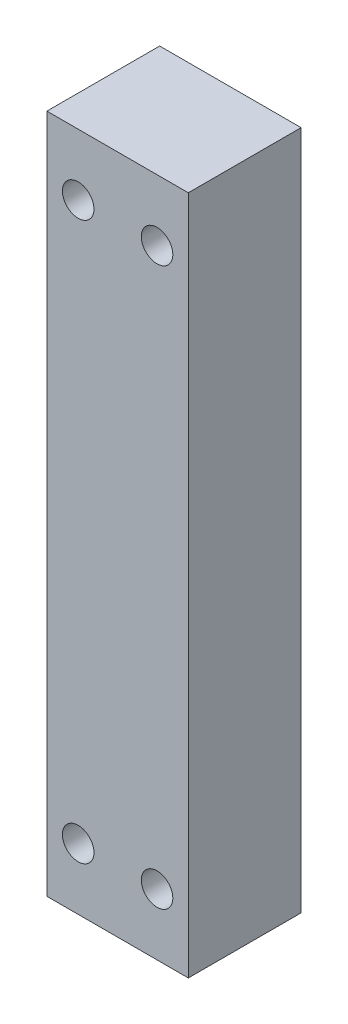
SolidWorks part; units mm, degrees
ref_plane "Plano frontal" through (0, 0, 0) normal (0, 0, 1) x (1, 0, 0)
ref_plane "Plano superior" through (0, 0, 0) normal (0, 1, 0) x (1, 0, 0)
ref_plane "Plano direito" through (0, 0, 0) normal (1, 0, 0) x (0, 0, -1)
sketch "Esboço1" plane through (0, 0, 0) normal (0, 0, 1) x (1, 0, 0)
  line L1 (2.8865, 58.6866) -> (29.7865, 58.6866)
  line L2 (2.8865, 58.6866) -> (2.8865, -70.6634)
  line L3 (2.8865, -70.6634) -> (29.7865, -70.6634)
  line L4 (29.7865, 58.6866) -> (29.7865, -70.6634)
  dimension "D1" = 129.35
  dimension "D2" = 26.9
base flange "Flange-base1" sketch "Esboço1" thickness 21.45 reverse thickness direction no parameters "D1"=4
sketch "Esboço7" plane through (0, 0, -21.45) normal (0, 0, -1) x (-1, 0, 0)
  line L0 (-29.7865, -5.9884) -> (-2.8865, -5.9884) construction
  line L1 (-29.7865, -70.6634) -> (-29.7865, 58.6866) construction
  line L2 (-2.8865, 58.6866) -> (-2.8865, -70.6634) construction
  line L3 (-16.3365, -58.9884) -> (-16.3365, 47.0116) construction
  line L4 (-23.8365, -58.9884) -> (-8.8365, -58.9884) construction
  line L5 (-23.8365, 47.0116) -> (-8.8365, 47.0116) construction
  circle A0 centre (-23.8365, 47.0116) radius 3
  circle A1 centre (-8.8365, 47.0116) radius 3
  circle A2 centre (-23.8365, -58.9884) radius 3
  circle A3 centre (-8.8365, -58.9884) radius 3
  point P6 (-16.3365, 47.0116)
  point P9 (-16.3365, -5.9884)
  point P15 (-16.3365, -58.9884)
extrude "Corte-extrusão1" cut sketch "Esboço7" against normal up to next (21.45 mm away) from surface at 0 starting at face at (16.3365, -5.9884, -21.45)
sketch "Esboço8" plane through (0, 0, 0) normal (0, 0, 1) x (1, 0, 0)
  line L0 (16.3365, -70.6634) -> (16.3365, 58.6866) construction
  line L1 (2.8865, -70.6634) -> (29.7865, -70.6634) construction
  line L2 (2.8865, 58.6866) -> (29.7865, 58.6866) construction
  circle A0 centre (16.3365, -5.9884) radius 5
sketch "Curva-Linhas1" [suppressed] plane through (0, 0, 0) normal (0, 1, 0) x (1, 0, 0)
sketch "Caixa delimitadora1" [suppressed] plane through (0, 0, 0) normal (0, 1, 0) x (1, 0, 0)
sheet metal parameters "Chapa metálica1" thickness 21.45 parameters "D1"=4
flat pattern "Padrão-Plano1" [suppressed]
sketch "Curva-Linhas2" plane through (0, 0, 0) normal (0, 1, 0) x (1, 0, 0)
sketch "Caixa delimitadora2" [suppressed] plane through (0, 0, 0) normal (0, 1, 0) x (1, 0, 0)
sheet metal parameters "Chapa metálica2" thickness 21.45 parameters "D1"=4
flat pattern "Padrão-Plano1"
sketch "Curva-Linhas2" plane through (0, 0, 0) normal (0, 1, 0) x (1, 0, 0)
sketch3d "Caixa delimitadora2" [suppressed]
  line L0 (29.7865, 58.6866, 0) -> (29.7865, -70.6634, 0) construction
  line L1 (2.8865, 58.6866, 0) -> (2.8865, -70.6634, 0) construction
  line L2 (29.7865, 58.6866, 0) -> (2.8865, 58.6866, 0) construction
  line L3 (29.7865, -70.6634, 0) -> (2.8865, -70.6634, 0) construction
